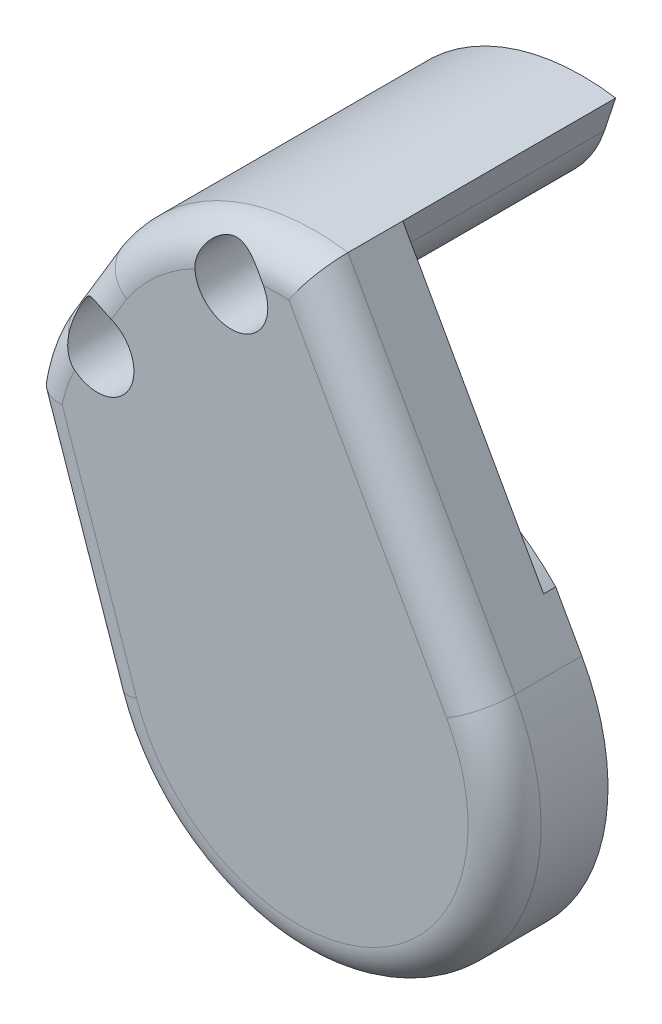
SolidWorks part; units mm, degrees
ref_plane "Front Plane" through (0, 0, 0) normal (0, 0, 1) x (1, 0, 0)
ref_plane "Top Plane" through (0, 0, 0) normal (0, 1, 0) x (1, 0, 0)
ref_plane "Right Plane" through (0, 0, 0) normal (1, 0, 0) x (0, 0, -1)
sketch "Sketch1" plane through (0, 0, 0) normal (0, 0, 1) x (1, 0, 0)
  line L0 (-21.5118, -23.5649) -> (-14.5118, -23.5649)
  line L1 (0, -9.9671) -> (2.0631, -3.7458)
  line L3 (-15.6677, -11.5659) -> (-19.5301, -18.0027)
  arc A1 (-19.5301, -18.0027) -> (-21.5118, -23.5649) centre (-6.6677, -25.7195) ccw
  arc A2 (-15.6677, -11.5659) -> (2.0631, -3.7458) centre (-0.6677, -21.5651) cw
  arc A3 (-14.5118, -23.5649) -> (0, -9.9671) centre (21.0043, -46.9259) cw
  circle A4 centre (-4.5301, -8.0036) radius 1.8
  circle A5 centre (-15.5301, -18.0027) radius 1.8
  point P10 (0, 0)
  point P12 (0, 0)
  dimension "D1" = 7
  dimension "D8" = 3.6
  dimension "D2" = 2.0631
  dimension "D3" = 3.7458
  dimension "D4" = 16.9817
  dimension "D5" = 15.5614
  dimension "D6" = 5.9817
  dimension "D7" = 5.5622
extrude "Boss-Extrude1" add sketch "Sketch1" along normal blind 21
sketch "Sketch2" plane through (0, 0, 21) normal (0, 0, 1) x (1, 0, 0)
  line L0 (-15.6677, -11.5659) -> (-19.5301, -18.0027) construction
  line L1 (-15.6677, -11.5659) -> (-19.5301, -18.0027)
  line L2 (2.0631, -3.7458) -> (15.7796, -28.3476)
  line L3 (-21.5118, -23.5649) -> (-15.1513, -42.1348)
  arc A0 (-19.5301, -18.0027) -> (-21.5118, -23.5649) centre (-6.6677, -25.7195) ccw construction
  arc A1 (2.0631, -3.7458) -> (-15.6677, -11.5659) centre (-0.6677, -21.5651) ccw construction
  arc A2 (-19.5301, -18.0027) -> (-21.5118, -23.5649) centre (-6.6677, -25.7195) ccw
  arc A3 (2.0631, -3.7458) -> (-15.6677, -11.5659) centre (-0.6677, -21.5651) ccw
  arc A4 (15.7796, -28.3476) -> (-15.1513, -42.1348) centre (0.9315, -36.6261) cw
  circle A5 centre (-15.5301, -18.0027) radius 1.8 construction
  circle A6 centre (-4.5301, -8.0036) radius 1.8 construction
  circle A7 centre (-15.5301, -18.0027) radius 1.8
  circle A8 centre (-4.5301, -8.0036) radius 1.8
  dimension "D1" = 17
  dimension "D2" = 22.4433
  dimension "D3" = 13.0611
extrude "Boss-Extrude2" add sketch "Sketch2" along normal blind 4 and the other way blind 4.5
sketch "Sketch3" plane through (0, 0, 16.5) normal (0, 0, -1) x (-1, 0, 0)
  circle A0 centre (-0.9315, -36.6261) radius 11.25
  point P3 (0, 0)
  dimension "D1" = 22.5
  dimension "D2" = 32.8803
  dimension "D3" = 22.4433
extrude "Cut-Extrude1" cut sketch "Sketch3" against normal blind 7
sketch "Sketch4" plane through (0, 0, 16.5) normal (0, 0, -1) x (-1, 0, 0)
  circle A0 centre (-0.9315, -36.6261) radius 13
  dimension "D1" = 26
extrude "Cut-Extrude2" cut sketch "Sketch4" against normal blind 1.5
sketch "Sketch5" plane through (0, 0, 25) normal (0, 0, 1) x (1, 0, 0)
  circle A0 centre (-4.5301, -8.0036) radius 3
  circle A1 centre (-15.5301, -18.0027) radius 3
  dimension "D1" = 6
extrude "Cut-Extrude3" cut sketch "Sketch5" against normal blind 12
fillet "Fillet1" radius 3 6 edges at (-20.7974, -20.6853, 25) (8.9213, -16.0467, 25) (7.8526, -52.1534, 25) (-17.5989, -14.7843, 25) (-7.9425, -5.0708, 25) (-18.3315, -32.8499, 25)
sketch "Sketch6" plane through (0, 0, 16.5) normal (0, 0, -1) x (-1, 0, 0)
  line L0 (-2.0631, -3.7458) -> (0, -9.9671)
  line L1 (-2.0631, -3.7458) -> (-13.6368, -24.5042)
  line L2 (-15.7796, -28.3476) -> (-2.0631, -3.7458) construction
  line L3 (10.6831, -18.5879) -> (8.6095, -21.8839)
  arc A0 (-13.6368, -24.5042) -> (8.6095, -21.8839) centre (-0.9315, -36.6261) cw
  arc A1 (0, -9.9671) -> (10.6831, -18.5879) centre (-21.0043, -46.9259) cw
  arc A2 (14.5118, -23.5649) -> (0, -9.9671) centre (-21.0043, -46.9259) ccw construction
  dimension "D1" = 42.5104
  dimension "D2" = 17.5603
  dimension "D3" = 3.2959
  dimension "D4" = 10.6831
  dimension "D5" = 2.0736
  dimension "D6" = 11.5737
extrude "Cut-Extrude4" cut sketch "Sketch6" against normal blind 1
fillet "Fillet2" radius 10 2 edges at (-14.5118, -23.5649, 8.25) (0, -9.9671, 8.75)
